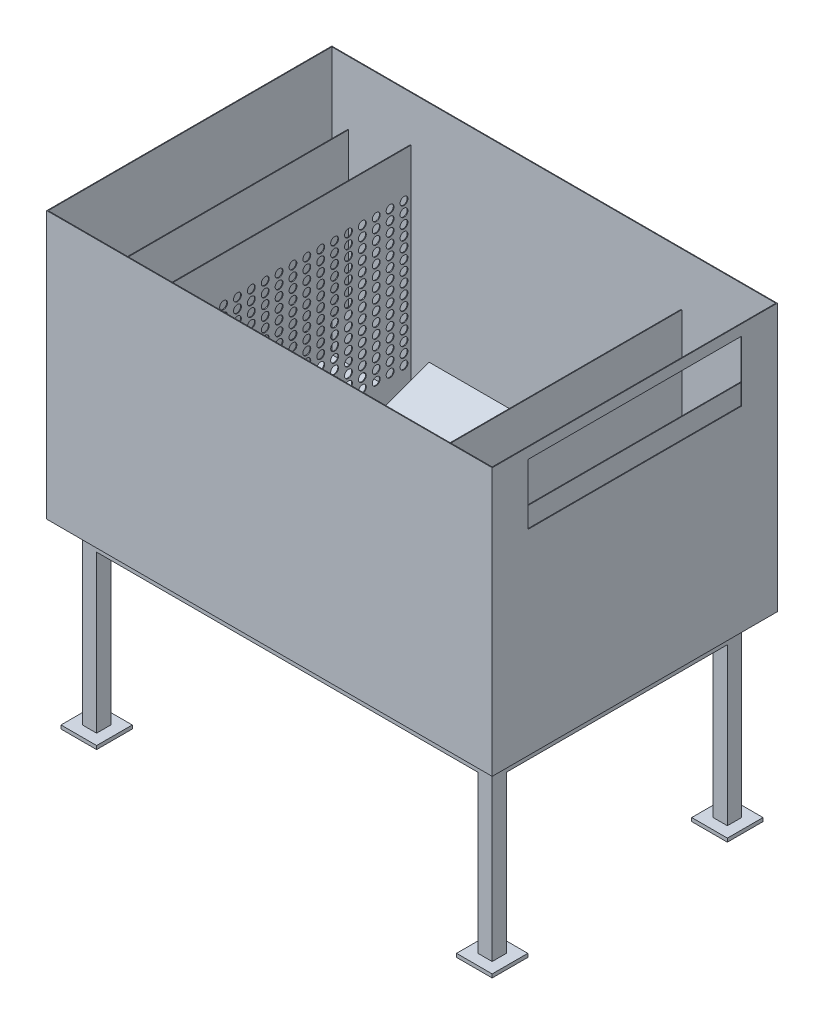
SolidWorks part; units mm, degrees
ref_plane "Спереди" through (0, 0, 0) normal (0, 0, 1) x (1, 0, 0)
ref_plane "Сверху" through (0, 0, 0) normal (0, 1, 0) x (1, 0, 0)
ref_plane "Справа" through (0, 0, 0) normal (1, 0, 0) x (0, 0, -1)
sketch "MASTER_FOOTPRINT" plane through (0, 0, 0) normal (0, 1, 0) x (1, 0, 0)
  line L1 (0, 0) -> (1250, 0)
  line L2 (0, 0) -> (0, 800)
  line L3 (0, 800) -> (1250, 800)
  line L4 (1250, 0) -> (1250, 800)
  dimension "D1" = 1250
  dimension "D2" = 800
extrude "BATH_BASE_PLATE" add sketch "MASTER_FOOTPRINT" along normal blind 750
shell "BATH_SHELL_2MM" thickness 2 removed face at (625, 750, -400)
sketch "Эскиз1" plane through (0, 0, 0) normal (1, 0, 0) x (0, 0, -1)
  circle A0 centre (400, 420) radius 50
extrude "INLET_D100_OPENING" cut sketch "Эскиз1" along normal blind 10
sketch "Эскиз2" plane through (0, 0, 0) normal (1, 0, 0) x (0, 0, -1)
  line L1 (80, 220) -> (720, 220)
  line L2 (80, 220) -> (80, 650)
  line L3 (80, 650) -> (720, 650)
  line L4 (720, 220) -> (720, 650)
extrude "INLET_IMPACT_BAFFLE" add sketch "Эскиз2" along normal blind 2 from offset 125 separate body
sketch "Эскиз3" plane through (0, 0, 0) normal (1, 0, 0) x (0, 0, -1)
  line L1 (30, 2) -> (770, 2)
  line L2 (30, 2) -> (30, 650)
  line L3 (30, 650) -> (770, 650)
  line L4 (770, 2) -> (770, 650)
  circle A0 centre (49.4737, 125) radius 11
  circle A1 centre (49.4737, 153.5) radius 11
  circle A2 centre (49.4737, 182) radius 11
  circle A3 centre (49.4737, 210.5) radius 11
  circle A4 centre (49.4737, 239) radius 11
  circle A5 centre (49.4737, 267.5) radius 11
  circle A6 centre (49.4737, 296) radius 11
  circle A7 centre (49.4737, 324.5) radius 11
  circle A8 centre (49.4737, 353) radius 11
  circle A9 centre (49.4737, 381.5) radius 11
  circle A10 centre (49.4737, 410) radius 11
  circle A11 centre (49.4737, 438.5) radius 11
  circle A12 centre (49.4737, 467) radius 11
  circle A13 centre (49.4737, 495.5) radius 11
  circle A14 centre (49.4737, 524) radius 11
  circle A15 centre (88.4211, 125) radius 11
  circle A16 centre (88.4211, 153.5) radius 11
  circle A17 centre (88.4211, 182) radius 11
  circle A18 centre (88.4211, 210.5) radius 11
  circle A19 centre (88.4211, 239) radius 11
  circle A20 centre (88.4211, 267.5) radius 11
  circle A21 centre (88.4211, 296) radius 11
  circle A22 centre (88.4211, 324.5) radius 11
  circle A23 centre (88.4211, 353) radius 11
  circle A24 centre (88.4211, 381.5) radius 11
  circle A25 centre (88.4211, 410) radius 11
  circle A26 centre (88.4211, 438.5) radius 11
  circle A27 centre (88.4211, 467) radius 11
  circle A28 centre (88.4211, 495.5) radius 11
  circle A29 centre (88.4211, 524) radius 11
  circle A30 centre (127.3684, 125) radius 11
  circle A31 centre (127.3684, 153.5) radius 11
  circle A32 centre (127.3684, 182) radius 11
  circle A33 centre (127.3684, 210.5) radius 11
  circle A34 centre (127.3684, 239) radius 11
  circle A35 centre (127.3684, 267.5) radius 11
  circle A36 centre (127.3684, 296) radius 11
  circle A37 centre (127.3684, 324.5) radius 11
  circle A38 centre (127.3684, 353) radius 11
  circle A39 centre (127.3684, 381.5) radius 11
  circle A40 centre (127.3684, 410) radius 11
  circle A41 centre (127.3684, 438.5) radius 11
  circle A42 centre (127.3684, 467) radius 11
  circle A43 centre (127.3684, 495.5) radius 11
  circle A44 centre (127.3684, 524) radius 11
  circle A45 centre (166.3158, 125) radius 11
  circle A46 centre (166.3158, 153.5) radius 11
  circle A47 centre (166.3158, 182) radius 11
  circle A48 centre (166.3158, 210.5) radius 11
  circle A49 centre (166.3158, 239) radius 11
  circle A50 centre (166.3158, 267.5) radius 11
  circle A51 centre (166.3158, 296) radius 11
  circle A52 centre (166.3158, 324.5) radius 11
  circle A53 centre (166.3158, 353) radius 11
  circle A54 centre (166.3158, 381.5) radius 11
  circle A55 centre (166.3158, 410) radius 11
  circle A56 centre (166.3158, 438.5) radius 11
  circle A57 centre (166.3158, 467) radius 11
  circle A58 centre (166.3158, 495.5) radius 11
  circle A59 centre (166.3158, 524) radius 11
  circle A60 centre (205.2632, 125) radius 11
  circle A61 centre (205.2632, 153.5) radius 11
  circle A62 centre (205.2632, 182) radius 11
  circle A63 centre (205.2632, 210.5) radius 11
  circle A64 centre (205.2632, 239) radius 11
  circle A65 centre (205.2632, 267.5) radius 11
  circle A66 centre (205.2632, 296) radius 11
  circle A67 centre (205.2632, 324.5) radius 11
  circle A68 centre (205.2632, 353) radius 11
  circle A69 centre (205.2632, 381.5) radius 11
  circle A70 centre (205.2632, 410) radius 11
  circle A71 centre (205.2632, 438.5) radius 11
  circle A72 centre (205.2632, 467) radius 11
  circle A73 centre (205.2632, 495.5) radius 11
  circle A74 centre (205.2632, 524) radius 11
  circle A75 centre (244.2105, 125) radius 11
  circle A76 centre (244.2105, 153.5) radius 11
  circle A77 centre (244.2105, 182) radius 11
  circle A78 centre (244.2105, 210.5) radius 11
  circle A79 centre (244.2105, 239) radius 11
  circle A80 centre (244.2105, 267.5) radius 11
  circle A81 centre (244.2105, 296) radius 11
  circle A82 centre (244.2105, 324.5) radius 11
  circle A83 centre (244.2105, 353) radius 11
  circle A84 centre (244.2105, 381.5) radius 11
  circle A85 centre (244.2105, 410) radius 11
  circle A86 centre (244.2105, 438.5) radius 11
  circle A87 centre (244.2105, 467) radius 11
  circle A88 centre (244.2105, 495.5) radius 11
  circle A89 centre (244.2105, 524) radius 11
  circle A90 centre (283.1579, 125) radius 11
  circle A91 centre (283.1579, 153.5) radius 11
  circle A92 centre (283.1579, 182) radius 11
  circle A93 centre (283.1579, 210.5) radius 11
  circle A94 centre (283.1579, 239) radius 11
  circle A95 centre (283.1579, 267.5) radius 11
  circle A96 centre (283.1579, 296) radius 11
  circle A97 centre (283.1579, 324.5) radius 11
  circle A98 centre (283.1579, 353) radius 11
  circle A99 centre (283.1579, 381.5) radius 11
  circle A100 centre (283.1579, 410) radius 11
  circle A101 centre (283.1579, 438.5) radius 11
  circle A102 centre (283.1579, 467) radius 11
  circle A103 centre (283.1579, 495.5) radius 11
  circle A104 centre (283.1579, 524) radius 11
  circle A105 centre (322.1053, 125) radius 11
  circle A106 centre (322.1053, 153.5) radius 11
  circle A107 centre (322.1053, 182) radius 11
  circle A108 centre (322.1053, 210.5) radius 11
  circle A109 centre (322.1053, 239) radius 11
  circle A110 centre (322.1053, 267.5) radius 11
  circle A111 centre (322.1053, 296) radius 11
  circle A112 centre (322.1053, 324.5) radius 11
  circle A113 centre (322.1053, 353) radius 11
  circle A114 centre (322.1053, 381.5) radius 11
  circle A115 centre (322.1053, 410) radius 11
  circle A116 centre (322.1053, 438.5) radius 11
  circle A117 centre (322.1053, 467) radius 11
  circle A118 centre (322.1053, 495.5) radius 11
  circle A119 centre (322.1053, 524) radius 11
  circle A120 centre (361.0526, 125) radius 11
  circle A121 centre (361.0526, 153.5) radius 11
  circle A122 centre (361.0526, 182) radius 11
  circle A123 centre (361.0526, 210.5) radius 11
  circle A124 centre (361.0526, 239) radius 11
  circle A125 centre (361.0526, 267.5) radius 11
  circle A126 centre (361.0526, 296) radius 11
  circle A127 centre (361.0526, 324.5) radius 11
  circle A128 centre (361.0526, 353) radius 11
  circle A129 centre (361.0526, 381.5) radius 11
  circle A130 centre (361.0526, 410) radius 11
  circle A131 centre (361.0526, 438.5) radius 11
  circle A132 centre (361.0526, 467) radius 11
  circle A133 centre (361.0526, 495.5) radius 11
  circle A134 centre (361.0526, 524) radius 11
  circle A135 centre (400, 125) radius 11
  circle A136 centre (400, 153.5) radius 11
  circle A137 centre (400, 182) radius 11
  circle A138 centre (400, 210.5) radius 11
  circle A139 centre (400, 239) radius 11
  circle A140 centre (400, 267.5) radius 11
  circle A141 centre (400, 296) radius 11
  circle A142 centre (400, 324.5) radius 11
  circle A143 centre (400, 353) radius 11
  circle A144 centre (400, 381.5) radius 11
  circle A145 centre (400, 410) radius 11
  circle A146 centre (400, 438.5) radius 11
  circle A147 centre (400, 467) radius 11
  circle A148 centre (400, 495.5) radius 11
  circle A149 centre (400, 524) radius 11
  circle A150 centre (438.9474, 125) radius 11
  circle A151 centre (438.9474, 153.5) radius 11
  circle A152 centre (438.9474, 182) radius 11
  circle A153 centre (438.9474, 210.5) radius 11
  circle A154 centre (438.9474, 239) radius 11
  circle A155 centre (438.9474, 267.5) radius 11
  circle A156 centre (438.9474, 296) radius 11
  circle A157 centre (438.9474, 324.5) radius 11
  circle A158 centre (438.9474, 353) radius 11
  circle A159 centre (438.9474, 381.5) radius 11
  circle A160 centre (438.9474, 410) radius 11
  circle A161 centre (438.9474, 438.5) radius 11
  circle A162 centre (438.9474, 467) radius 11
  circle A163 centre (438.9474, 495.5) radius 11
  circle A164 centre (438.9474, 524) radius 11
  circle A165 centre (477.8947, 125) radius 11
  circle A166 centre (477.8947, 153.5) radius 11
  circle A167 centre (477.8947, 182) radius 11
  circle A168 centre (477.8947, 210.5) radius 11
  circle A169 centre (477.8947, 239) radius 11
  circle A170 centre (477.8947, 267.5) radius 11
  circle A171 centre (477.8947, 296) radius 11
  circle A172 centre (477.8947, 324.5) radius 11
  circle A173 centre (477.8947, 353) radius 11
  circle A174 centre (477.8947, 381.5) radius 11
  circle A175 centre (477.8947, 410) radius 11
  circle A176 centre (477.8947, 438.5) radius 11
  circle A177 centre (477.8947, 467) radius 11
  circle A178 centre (477.8947, 495.5) radius 11
  circle A179 centre (477.8947, 524) radius 11
  circle A180 centre (516.8421, 125) radius 11
  circle A181 centre (516.8421, 153.5) radius 11
  circle A182 centre (516.8421, 182) radius 11
  circle A183 centre (516.8421, 210.5) radius 11
  circle A184 centre (516.8421, 239) radius 11
  circle A185 centre (516.8421, 267.5) radius 11
  circle A186 centre (516.8421, 296) radius 11
  circle A187 centre (516.8421, 324.5) radius 11
  circle A188 centre (516.8421, 353) radius 11
  circle A189 centre (516.8421, 381.5) radius 11
  circle A190 centre (516.8421, 410) radius 11
  circle A191 centre (516.8421, 438.5) radius 11
  circle A192 centre (516.8421, 467) radius 11
  circle A193 centre (516.8421, 495.5) radius 11
  circle A194 centre (516.8421, 524) radius 11
  circle A195 centre (555.7895, 125) radius 11
  circle A196 centre (555.7895, 153.5) radius 11
  circle A197 centre (555.7895, 182) radius 11
  circle A198 centre (555.7895, 210.5) radius 11
  circle A199 centre (555.7895, 239) radius 11
  circle A200 centre (555.7895, 267.5) radius 11
  circle A201 centre (555.7895, 296) radius 11
  circle A202 centre (555.7895, 324.5) radius 11
  circle A203 centre (555.7895, 353) radius 11
  circle A204 centre (555.7895, 381.5) radius 11
  circle A205 centre (555.7895, 410) radius 11
  circle A206 centre (555.7895, 438.5) radius 11
  circle A207 centre (555.7895, 467) radius 11
  circle A208 centre (555.7895, 495.5) radius 11
  circle A209 centre (555.7895, 524) radius 11
  circle A210 centre (594.7368, 125) radius 11
  circle A211 centre (594.7368, 153.5) radius 11
  circle A212 centre (594.7368, 182) radius 11
  circle A213 centre (594.7368, 210.5) radius 11
  circle A214 centre (594.7368, 239) radius 11
  circle A215 centre (594.7368, 267.5) radius 11
  circle A216 centre (594.7368, 296) radius 11
  circle A217 centre (594.7368, 324.5) radius 11
  circle A218 centre (594.7368, 353) radius 11
  circle A219 centre (594.7368, 381.5) radius 11
  circle A220 centre (594.7368, 410) radius 11
  circle A221 centre (594.7368, 438.5) radius 11
  circle A222 centre (594.7368, 467) radius 11
  circle A223 centre (594.7368, 495.5) radius 11
  circle A224 centre (594.7368, 524) radius 11
  circle A225 centre (633.6842, 125) radius 11
  circle A226 centre (633.6842, 153.5) radius 11
  circle A227 centre (633.6842, 182) radius 11
  circle A228 centre (633.6842, 210.5) radius 11
  circle A229 centre (633.6842, 239) radius 11
  circle A230 centre (633.6842, 267.5) radius 11
  circle A231 centre (633.6842, 296) radius 11
  circle A232 centre (633.6842, 324.5) radius 11
  circle A233 centre (633.6842, 353) radius 11
  circle A234 centre (633.6842, 381.5) radius 11
  circle A235 centre (633.6842, 410) radius 11
  circle A236 centre (633.6842, 438.5) radius 11
  circle A237 centre (633.6842, 467) radius 11
  circle A238 centre (633.6842, 495.5) radius 11
  circle A239 centre (633.6842, 524) radius 11
  circle A240 centre (672.6316, 125) radius 11
  circle A241 centre (672.6316, 153.5) radius 11
  circle A242 centre (672.6316, 182) radius 11
  circle A243 centre (672.6316, 210.5) radius 11
  circle A244 centre (672.6316, 239) radius 11
  circle A245 centre (672.6316, 267.5) radius 11
  circle A246 centre (672.6316, 296) radius 11
  circle A247 centre (672.6316, 324.5) radius 11
  circle A248 centre (672.6316, 353) radius 11
  circle A249 centre (672.6316, 381.5) radius 11
  circle A250 centre (672.6316, 410) radius 11
  circle A251 centre (672.6316, 438.5) radius 11
  circle A252 centre (672.6316, 467) radius 11
  circle A253 centre (672.6316, 495.5) radius 11
  circle A254 centre (672.6316, 524) radius 11
  circle A255 centre (711.5789, 125) radius 11
  circle A256 centre (711.5789, 153.5) radius 11
  circle A257 centre (711.5789, 182) radius 11
  circle A258 centre (711.5789, 210.5) radius 11
  circle A259 centre (711.5789, 239) radius 11
  circle A260 centre (711.5789, 267.5) radius 11
  circle A261 centre (711.5789, 296) radius 11
  circle A262 centre (711.5789, 324.5) radius 11
  circle A263 centre (711.5789, 353) radius 11
  circle A264 centre (711.5789, 381.5) radius 11
  circle A265 centre (711.5789, 410) radius 11
  circle A266 centre (711.5789, 438.5) radius 11
  circle A267 centre (711.5789, 467) radius 11
  circle A268 centre (711.5789, 495.5) radius 11
  circle A269 centre (711.5789, 524) radius 11
  circle A270 centre (750.5263, 125) radius 11
  circle A271 centre (750.5263, 153.5) radius 11
  circle A272 centre (750.5263, 182) radius 11
  circle A273 centre (750.5263, 210.5) radius 11
  circle A274 centre (750.5263, 239) radius 11
  circle A275 centre (750.5263, 267.5) radius 11
  circle A276 centre (750.5263, 296) radius 11
  circle A277 centre (750.5263, 324.5) radius 11
  circle A278 centre (750.5263, 353) radius 11
  circle A279 centre (750.5263, 381.5) radius 11
  circle A280 centre (750.5263, 410) radius 11
  circle A281 centre (750.5263, 438.5) radius 11
  circle A282 centre (750.5263, 467) radius 11
  circle A283 centre (750.5263, 495.5) radius 11
  circle A284 centre (750.5263, 524) radius 11
extrude "DISTRIBUTOR_D22" add sketch "Эскиз3" along normal blind 2 from offset 250 separate body
sketch "Эскиз4" plane through (0, 0, 0) normal (1, 0, 0) x (0, 0, -1)
  line L1 (50, 320) -> (750, 320)
  line L2 (50, 320) -> (50, 650)
  line L3 (50, 650) -> (750, 650)
  line L4 (750, 320) -> (750, 650)
extrude "OUTLET_SUBMERGED_BAFFLE" add sketch "Эскиз4" along normal blind 2 from offset 1030 separate body
sketch "Эскиз5" plane through (0, 0, 0) normal (1, 0, 0) x (0, 0, -1)
  line L1 (5, 2) -> (795, 2)
  line L2 (5, 2) -> (5, 550)
  line L3 (5, 550) -> (795, 550)
  line L4 (795, 2) -> (795, 550)
extrude "OVERFLOW_WEIR_Z550" add sketch "Эскиз5" along normal blind 2 from offset 1190 separate body
sketch "Эскиз6" plane through (0, 0, 0) normal (1, 0, 0) x (0, 0, -1)
  line L1 (100, 550) -> (700, 550)
  line L2 (100, 550) -> (100, 720)
  line L3 (100, 720) -> (700, 720)
  line L4 (700, 550) -> (700, 720)
extrude "OUTLET_WEIR_SLOT_W600" cut sketch "Эскиз6" along normal blind 10 from offset 1245
sketch "Эскиз7" plane through (0, 0, 0) normal (1, 0, 0) x (0, 0, -1)
  line L0 (2, -1) -> (2, 120)
  line L1 (2, 120) -> (330, -1)
  line L2 (330, -1) -> (2, -1)
  line L3 (798, -1) -> (798, 120)
  line L4 (798, 120) -> (470, -1)
  line L5 (470, -1) -> (798, -1)
extrude "SLOPED_SEDIMENT_FLOOR" add sketch "Эскиз7" along normal blind 725 from offset 275
sketch3d "SCREW_AXIS_30DEG_REFERENCE"
  line L0 (400, 70, -400) -> (1350, 618.4828, -400)
sketch "Эскиз8" plane through (0, 0, 0) normal (0, 1, 0) x (1, 0, 0)
  line L1 (50, 50) -> (90, 50)
  line L2 (50, 50) -> (50, 90)
  line L3 (50, 90) -> (90, 90)
  line L4 (90, 50) -> (90, 90)
  line L6 (50, 710) -> (90, 710)
  line L7 (50, 710) -> (50, 750)
  line L8 (50, 750) -> (90, 750)
  line L9 (90, 710) -> (90, 750)
  line L11 (1160, 50) -> (1200, 50)
  line L12 (1160, 50) -> (1160, 90)
  line L13 (1160, 90) -> (1200, 90)
  line L14 (1200, 50) -> (1200, 90)
  line L16 (1160, 710) -> (1200, 710)
  line L17 (1160, 710) -> (1160, 750)
  line L18 (1160, 750) -> (1200, 750)
  line L19 (1200, 710) -> (1200, 750)
extrude "FRAME_LEGS_40X40_H500" add sketch "Эскиз8" against normal blind 500
sketch "Эскиз9" plane through (0, 0, 0) normal (0, 1, 0) x (1, 0, 0)
  line L1 (50, 50) -> (1200, 50)
  line L2 (50, 50) -> (50, 90)
  line L3 (50, 90) -> (1200, 90)
  line L4 (1200, 50) -> (1200, 90)
  line L6 (50, 710) -> (1200, 710)
  line L7 (50, 710) -> (50, 750)
  line L8 (50, 750) -> (1200, 750)
  line L9 (1200, 710) -> (1200, 750)
extrude "FRAME_LONGITUDINAL_RAILS" add sketch "Эскиз9" against normal blind 40 from offset 20 offset against normal yes
sketch "Эскиз10" plane through (0, 0, 0) normal (0, 1, 0) x (1, 0, 0)
  line L1 (50, 90) -> (90, 90)
  line L2 (50, 90) -> (50, 710)
  line L3 (50, 710) -> (90, 710)
  line L4 (90, 90) -> (90, 710)
  line L6 (1160, 90) -> (1200, 90)
  line L7 (1160, 90) -> (1160, 710)
  line L8 (1160, 710) -> (1200, 710)
  line L9 (1200, 90) -> (1200, 710)
extrude "FRAME_TRANSVERSE_RAILS" add sketch "Эскиз10" against normal blind 40 from offset 20 offset against normal yes
sketch "Эскиз11" plane through (0, 0, 0) normal (0, 1, 0) x (1, 0, 0)
  line L1 (20, 20) -> (120, 20)
  line L2 (20, 20) -> (20, 120)
  line L3 (20, 120) -> (120, 120)
  line L4 (120, 20) -> (120, 120)
  line L6 (20, 680) -> (120, 680)
  line L7 (20, 680) -> (20, 780)
  line L8 (20, 780) -> (120, 780)
  line L9 (120, 680) -> (120, 780)
  line L11 (1130, 20) -> (1230, 20)
  line L12 (1130, 20) -> (1130, 120)
  line L13 (1130, 120) -> (1230, 120)
  line L14 (1230, 20) -> (1230, 120)
  line L16 (1130, 680) -> (1230, 680)
  line L17 (1130, 680) -> (1130, 780)
  line L18 (1130, 780) -> (1230, 780)
  line L19 (1230, 680) -> (1230, 780)
extrude "FRAME_FOOT_PADS_100X100" add sketch "Эскиз11" against normal blind 10 from offset 500 offset against normal yes
equation "\"AI_Q_Peak\"= 0.006"
equation "\"AI_B_Bath\" = 800"
equation "\"AI_L_Settle\" = 800"
equation "\"AI_L_Inlet\"= 250"
equation "\"AI_L_Outlet\"= 200"
equation "\"AI_L_Bath\" = 1250"
equation "\"AI_H_Water\"= 550"
equation "\"AI_H_Freeboard\"= 200"
equation "\"AI_H_Bath\"= 750"
equation "\"AI_Shell_Thickness\"= 2"
equation "\"AI_Inlet_DN\"= 100"
equation "\"AI_Weir_Width\"= 600"
equation "\"AI_Inlet_Baffle_Offset\"= 125"
equation "\"AI_Distributor_Open_Area\"= 0.28"
equation "\"AI_Distributor_Hole_Dia\"= 22"
equation "\"AI_Distributor_Blind_Zone\"= 110"
equation "\"AI_Outlet_Baffle_Depth\"= 250"
equation "\"AI_Screw_Diameter\"= 100"
equation "\"AI_Screw_Pitch\"= 100"
equation "\"AI_Screw_Angle\"= 30"
equation "\"AI_Screw_Rpm\"= 15"
equation "\"AI_Screw_Clearance\"= 5"
equation "\"AI_Liner_Thickness\"= 5"
equation "\"AI_Discharge_Height\"= 650"
equation "\"AI_Frame_Height\"= 500"
equation "\"D1@MASTER_FOOTPRINT\" = \"AI_L_Bath\""
equation "\"D2@MASTER_FOOTPRINT\" = \"AI_B_Bath\""
equation "\"D1@BATH_BASE_PLATE\" = \"AI_H_Bath\""
